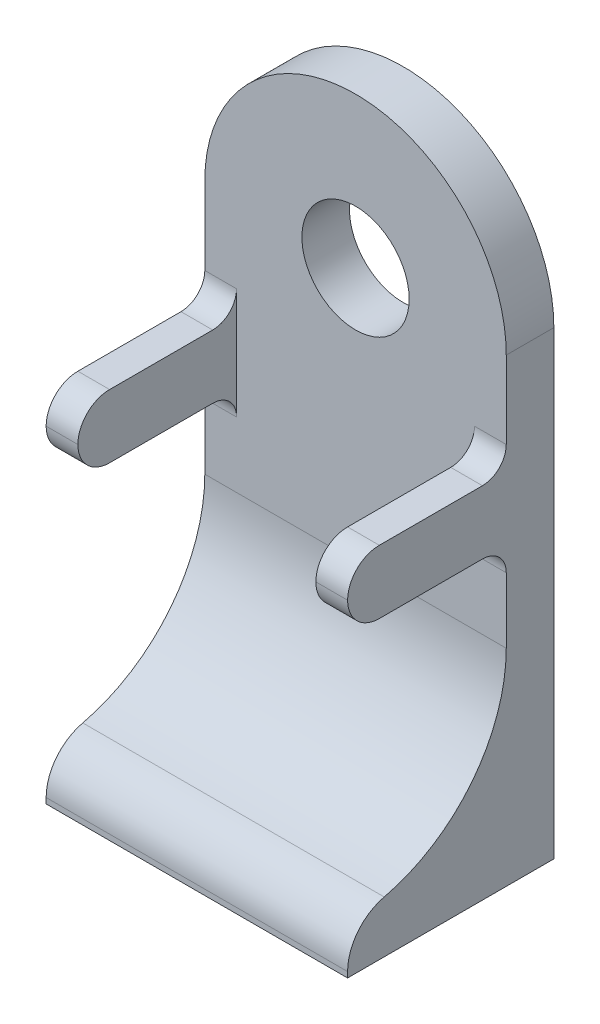
SolidWorks part; units mm, degrees
material "ABS"
ref_plane "Alzado" through (0, 0, 0) normal (0, 0, 1) x (1, 0, 0)
ref_plane "Planta" through (0, 0, 0) normal (0, 1, 0) x (1, 0, 0)
ref_plane "Vista lateral" through (0, 0, 0) normal (1, 0, 0) x (0, 0, -1)
sketch "Croquis2" plane through (0, 0, 0) normal (0, 0, 1) x (1, 0, 0)
  line L0 (-9.5, 0) -> (-9.5, -29)
  line L1 (-9.5, -29) -> (9.5, -29)
  line L2 (9.5, -29) -> (9.5, 0)
  circle A0 centre (0, 0) radius 3.38
  arc A1 (-9.5, 0) -> (9.5, 0) centre (0, 0) cw
  point P8 (0, 9.5)
  point P10 (0, -29)
  dimension "D1" = 6.76
  dimension "D2" = 9.5
  dimension "D3" = 29
extrude "Saliente-Extruir1" add sketch "Croquis2" along normal blind 3
sketch "Croquis4" plane through (0, 0, 3) normal (0, 0, 1) x (1, 0, 0)
  line L0 (9.5, -29) -> (9.5, 0) construction
  line L1 (-9.5, -29) -> (9.5, -29)
  line L2 (-9.5, -29) -> (-9.5, -26)
  line L3 (-9.5, -26) -> (9.5, -26)
  line L4 (9.5, -29) -> (9.5, -26)
  dimension "D1" = 3
extrude "Saliente-Extruir2" add sketch "Croquis4" along normal blind 10
fillet "Redondeo1" radius 10 1 edges at (0, -26, 3) type face fillet first side face at (3.38, 0, 3) second side face at (0, -26, 8)
sketch "Croquis7" plane through (0, 0, 3) normal (0, 0, 1) x (1, 0, 0)
  line L0 (-7.5, -6.38) -> (-7.5, -10.38)
  line L2 (7.5, -6.38) -> (7.5, -10.38)
  line L3 (-7.5, -6.38) -> (-9.5, -6.38)
  line L4 (-9.5, 0) -> (-9.5, -16) construction
  line L5 (7.5, -6.38) -> (9.5, -6.38)
  line L6 (9.5, -16) -> (9.5, 0) construction
  line L7 (7.5, -10.38) -> (9.5, -10.38)
  line L8 (9.5, -10.38) -> (9.5, -6.38)
  line L9 (-7.5, -10.38) -> (-9.5, -10.38)
  line L10 (-9.5, -10.38) -> (-9.5, -6.38)
  circle A0 centre (0, 0) radius 3.38 construction
  point P15 (0, -3.38)
  dimension "D1" = 15
  dimension "D2" = 3
  dimension "D3" = 4
extrude "Saliente-Extruir4" add sketch "Croquis7" along normal blind 10
fillet "Redondeo4" radius 1.5 4 edges at (8.5, -6.38, 3) (8.5, -10.38, 3) (-8.5, -10.38, 3) (-8.5, -6.38, 3)
fillet "Redondeo5" radius 2 4 edges at (8.5, -10.38, 13) (8.5, -6.38, 13) (-8.5, -10.38, 13) (-8.5, -6.38, 13)
fillet "Redondeo6" radius 3 1 edges at (0, -26, 13)
